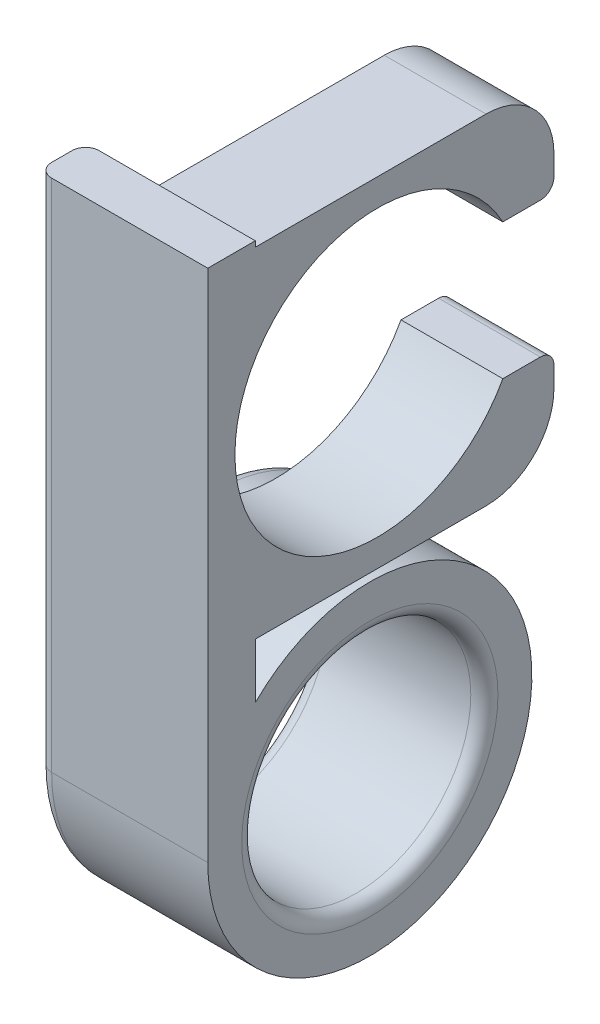
SolidWorks part; units mm, degrees
ref_plane "Front Plane" through (0, 0, 0) normal (0, 0, 1) x (1, 0, 0)
ref_plane "Top Plane" through (0, 0, 0) normal (0, 1, 0) x (1, 0, 0)
ref_plane "Right Plane" through (0, 0, 0) normal (1, 0, 0) x (0, 0, -1)
sketch "Sketch1" plane through (0, 0, 0) normal (1, 0, 0) x (0, 0, -1)
  circle A0 centre (0, 0) radius 16.875
  circle A1 centre (0, 0) radius 23.875
  dimension "D1" = 33.75
  dimension "D2" = 7
extrude "Boss-Extrude1" add sketch "Sketch1" along normal blind 25 contours A1 | A0
sketch "Sketch2" plane through (0, 0, 0) normal (0, 1, 0) x (1, 0, 0)
  line L0 (25, -23.875) -> (25, 23.875) construction
  line L1 (0, -23.875) -> (25, -23.875)
  line L2 (0, -23.875) -> (0, -16.875)
  line L3 (0, -16.875) -> (25, -16.875)
  line L4 (25, -23.875) -> (25, -16.875)
  line L5 (25, -16.875) -> (25, 16.875) construction
extrude "Boss-Extrude2" add sketch "Sketch2" along normal blind 75.83
sketch "Sketch4" plane through (25, 0, 0) normal (-1, 0, 0) x (0, 0, 1)
  line L0 (-1.125, 50) -> (23.875, 50) construction
  line L1 (23.875, 75.83) -> (23.875, 0) construction
  line L2 (-1.125, 29) -> (-1.125, 71)
  line L3 (-1.125, 25) -> (-1.125, 75)
  line L4 (-1.125, 75) -> (23.875, 75)
  line L5 (23.875, 75) -> (23.875, 25)
  line L6 (23.875, 25) -> (-1.125, 25)
  line L7 (-1.125, 75) -> (-27.125, 75)
  line L8 (-27.125, 75) -> (-27.125, 25)
  line L9 (-27.125, 25) -> (-1.125, 25)
  line L10 (-27.125, 60) -> (-19.5912, 60)
  line L11 (-27.125, 40) -> (-19.5912, 40)
  circle A0 centre (-1.125, 50) radius 11
  circle A1 centre (-1.125, 50) radius 21
  arc A2 (16.875, 16.8893) -> (23.875, 0) centre (0, 0) ccw construction
  point P13 (-1.125, 50)
  line M22 (16.875, 16.8893) -> (16.875, 75.83)
  dimension "D1" = 22
  dimension "D2" = 42
  dimension "D3" = 50
  dimension "D4" = 25
  dimension "D5" = 50
  dimension "D6" = 26
  dimension "D7" = 20
extrude "Boss-Extrude3" add sketch "Sketch4" along normal blind 15 contours A1 L3 L4 M22 | L3 A1 L6 M22 | L3 A1 L10 L8 L7 | L11 A1 L3 L9 L8 region at (25, 29.0768, 9.9007) region at (25, 30.7423, -17.5113) region at (25, 69.2577, -17.5113) region at (25, 70.9232, 9.9007)
extrude "Cut-Extrude1" cut sketch "Sketch4<4>" along normal up to surface (15 mm away) contours L0 A0 L2 A1 M22 | A0 L0 A1 L2 M22 | L0 A1 M22 | L0 A1 M22 region at (25, 61.1322, 8.5604) region at (25, 38.8678, 8.5604) region at (25, 54.0979, 18.0827) region at (25, 45.9021, 18.0827) up to face at (10, 68.2806, -8.0657)
sketch "Sketch4<4>" plane through (25, 0, 0) normal (-1, 0, 0) x (0, 0, 1) same geometry as "Sketch4"
fillet "Fillet1" radius 10 2 edges at (17.5, 25, -27.125) (17.5, 75, -27.125)
fillet "Fillet2" radius 2 5 edges at (25, 0, -16.875) (0, 37.915, 23.875) (0, 46.3597, 16.875) (0, -9.1413, -22.0557) (0, 0, -16.875)
fillet "Fillet3" radius 2 2 edges at (17.5, 40, -27.125) (17.5, 60, -27.125)
